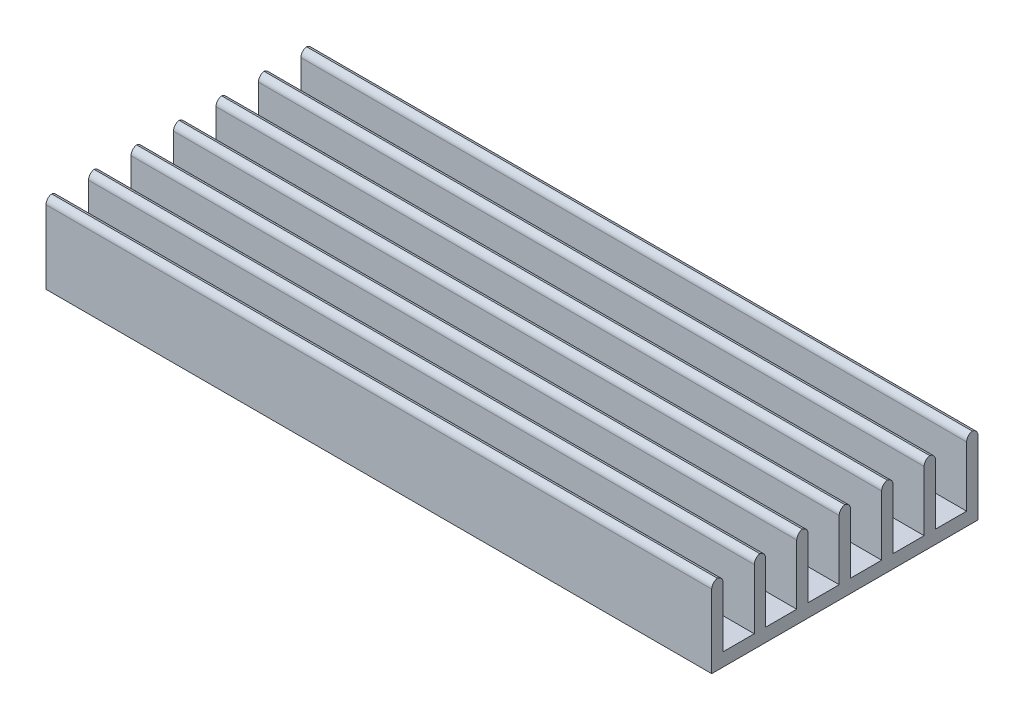
SolidWorks part; units mm, degrees
ref_plane "前视基准面" through (0, 0, 0) normal (0, 0, 1) x (1, 0, 0)
ref_plane "上视基准面" through (0, 0, 0) normal (0, 1, 0) x (1, 0, 0)
ref_plane "右视基准面" through (0, 0, 0) normal (1, 0, 0) x (0, 0, -1)
other "Configuration Table"
sketch "草图1" plane through (0, 0, 0) normal (0, 1, 0) x (1, 0, 0)
  line L1 (-25, 10) -> (25, 10)
  line L2 (-25, 10) -> (-25, -10)
  line L3 (-25, -10) -> (25, -10)
  line L4 (25, 10) -> (25, -10)
  line L5 (-25, 10) -> (25, -10) construction
  line L6 (-25, -10) -> (25, 10) construction
  point P0 (0, 0)
  dimension "D1" = 50
  dimension "D2" = 20
extrude "凸台-拉伸1" add sketch "草图1" along normal blind 6
sketch "草图2" plane through (0, 6, 0) normal (0, 1, 0) x (1, 0, 0)
  line L0 (25, -10) -> (25, 10) construction
  line L1 (-25, 0.425) -> (25, 0.425)
  line L2 (-25, 0.425) -> (-25, -0.425)
  line L3 (-25, -0.425) -> (25, -0.425)
  line L12 (25, 0.425) -> (25, -0.425)
  line L13 (-25, 0.425) -> (25, -0.425) construction
  line L14 (-25, -0.425) -> (25, 0.425) construction
  line L15 (-33.7892, 13.868) -> (-33.7892, -15.537) construction
  line L16 (-25, -2.765) -> (25, -2.765)
  line L17 (-25, -2.765) -> (-25, -3.615)
  line L18 (-25, -3.615) -> (25, -3.615)
  line L19 (25, -2.765) -> (25, -3.615)
  line L20 (-25, -2.765) -> (25, -3.615) construction
  line L21 (-25, -3.615) -> (25, -2.765) construction
  line L22 (-25, -5.955) -> (25, -5.955)
  line L23 (-25, -5.955) -> (-25, -6.805)
  line L24 (-25, -6.805) -> (25, -6.805)
  line L25 (25, -5.955) -> (25, -6.805)
  line L26 (-25, -5.955) -> (25, -6.805) construction
  line L27 (-25, -6.805) -> (25, -5.955) construction
  line L28 (-25, -9.145) -> (25, -9.145)
  line L29 (-25, -9.145) -> (-25, -9.995)
  line L30 (-25, -9.995) -> (25, -9.995)
  line L31 (25, -9.145) -> (25, -9.995)
  line L32 (-25, -9.145) -> (25, -9.995) construction
  line L33 (-25, -9.995) -> (25, -9.145) construction
  line L34 (-25, 3.615) -> (25, 3.615)
  line L35 (-25, 3.615) -> (-25, 2.765)
  line L36 (-25, 2.765) -> (25, 2.765)
  line L37 (25, 3.615) -> (25, 2.765)
  line L38 (-25, 3.615) -> (25, 2.765) construction
  line L39 (-25, 2.765) -> (25, 3.615) construction
  line L40 (-25, 6.805) -> (25, 6.805)
  line L41 (-25, 6.805) -> (-25, 5.955)
  line L42 (-25, 5.955) -> (25, 5.955)
  line L43 (25, 6.805) -> (25, 5.955)
  line L44 (-25, 6.805) -> (25, 5.955) construction
  line L45 (-25, 5.955) -> (25, 6.805) construction
  line L46 (-25, 9.995) -> (25, 9.995)
  line L47 (-25, 9.995) -> (-25, 9.145)
  line L48 (-25, 9.145) -> (25, 9.145)
  line L49 (25, 9.995) -> (25, 9.145)
  line L50 (-25, 9.995) -> (25, 9.145) construction
  line L51 (-25, 9.145) -> (25, 9.995) construction
  point P0 (0, 0)
  point P11 (0, -3.19)
  point P16 (0, -6.38)
  point P21 (0, -9.57)
  point P26 (0, 3.19)
  point P31 (0, 6.38)
  point P36 (0, 9.57)
  dimension "D1" = 0.85
extrude "切除-拉伸1" cut sketch "草图2" against normal blind 5
fillet "圆角1" radius 0.5 14 edges at (0, 6, 10) (0, 6, -10) (0, 6, 9.145) (0, 6, 6.805) (0, 6, 5.955) (0, 6, 3.615) (0, 6, 2.765) (0, 6, 0.425) (0, 6, -0.425) (0, 6, -2.765) (0, 6, -3.615) (0, 6, -6.805) (0, 6, -5.955) (0, 6, -9.145)
